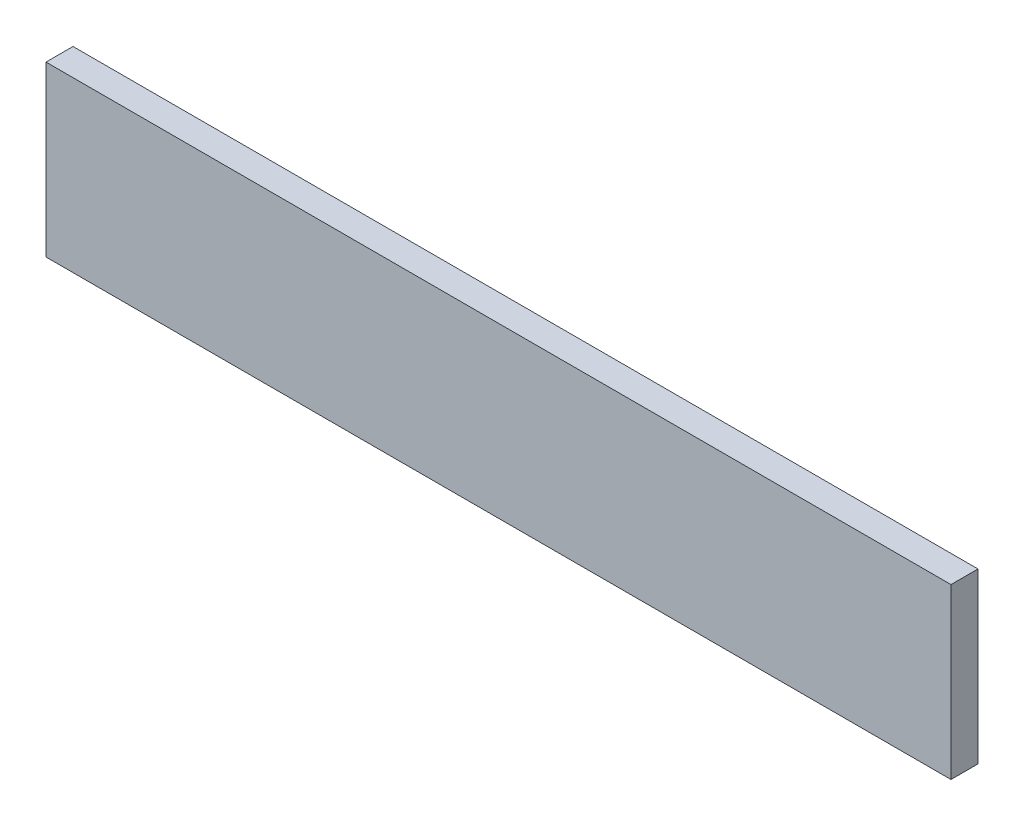
SolidWorks part; units mm, degrees
ref_plane "Front Plane" through (0, 0, 0) normal (0, 0, 1) x (1, 0, 0)
ref_plane "Top Plane" through (0, 0, 0) normal (0, 1, 0) x (1, 0, 0)
ref_plane "Right Plane" through (0, 0, 0) normal (1, 0, 0) x (0, 0, -1)
sketch "Sketch1" plane through (0, 0, 0) normal (0, 0, 1) x (1, 0, 0)
  line L1 (0, 119.05) -> (-638.1, 119.05)
  line L2 (0, 119.05) -> (0, 0)
  line L3 (0, 0) -> (-638.1, 0)
  line L4 (-638.1, 119.05) -> (-638.1, 0)
  dimension "D1" = 119.05
  dimension "D2" = 638.1
extrude "Boss-Extrude1" add sketch "Sketch1" along normal blind 19.05
